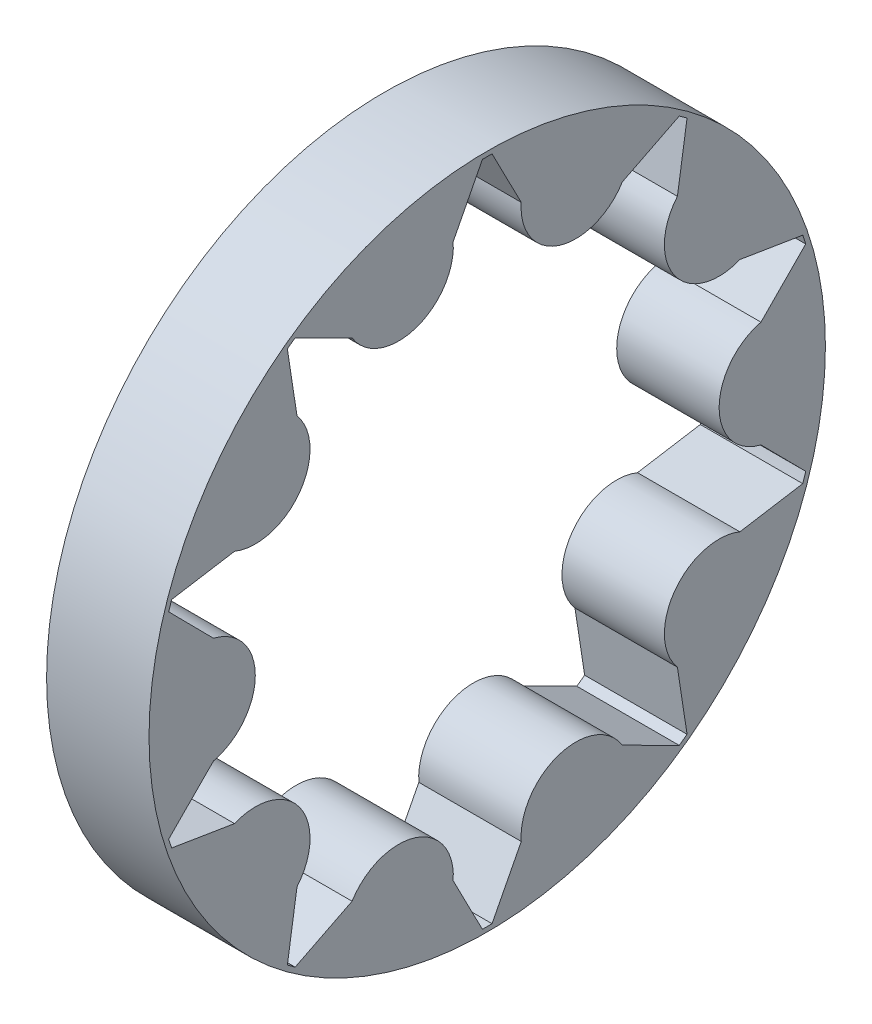
SolidWorks part; units mm, degrees
ref_plane "Front Plane" through (0, 0, 0) normal (0, 0, 1) x (1, 0, 0)
ref_plane "Top Plane" through (0, 0, 0) normal (0, 1, 0) x (1, 0, 0)
ref_plane "Right Plane" through (0, 0, 0) normal (1, 0, 0) x (0, 0, -1)
sketch "Sketch1" plane through (0, 0, 0) normal (1, 0, 0) x (0, 0, -1)
  line L0 (0, 0) -> (0, 17.25)
  line L1 (0, 0) -> (10.1393, 13.9555)
  line L4 (10.1393, 13.9555) -> (9.936, 14.101)
  line L5 (9.936, 14.101) -> (6.9922, 12.6205)
  line L6 (0, 0) -> (3.7082, 11.4127) construction
  line L7 (0.25, 17.2482) -> (1.7614, 14.3201)
  line L8 (10.1393, 13.9555) -> (10.2862, 14.1578)
  line L9 (0, 17.25) -> (0, 17.5)
  circle A0 centre (0, 0) radius 12
  circle A1 centre (0, 0) radius 17.25
  circle A2 centre (0, 0) radius 14.4281 construction
  arc A3 (1.7614, 14.3201) -> (6.9922, 12.6205) centre (4.5826, 14.1037) ccw
  circle A4 centre (0, 0) radius 17.5
  point P10 (10.0376, 14.0283)
  point P13 (0.125, 17.2491)
  dimension "D1" = 24
  dimension "D2" = 34.5
  dimension "D3" = 0.25
  dimension "D6" = 35
  dimension "D4" = 36
  dimension "D5" = 5.5
extrude "Boss-Extrude1" add sketch "Sketch1" along normal blind 5.3 contours L7 A3 L5 A1 | L8 A4 L9 A1 region at (0, 17.375, -0.1088) region at (0, 14.3238, -4.6541)
pattern_circular "CirPattern2" count 10 over 360 about axis through (5.3, 0, 0) along (-1, 0, 0) of "Boss-Extrude1" reverse direction yes
